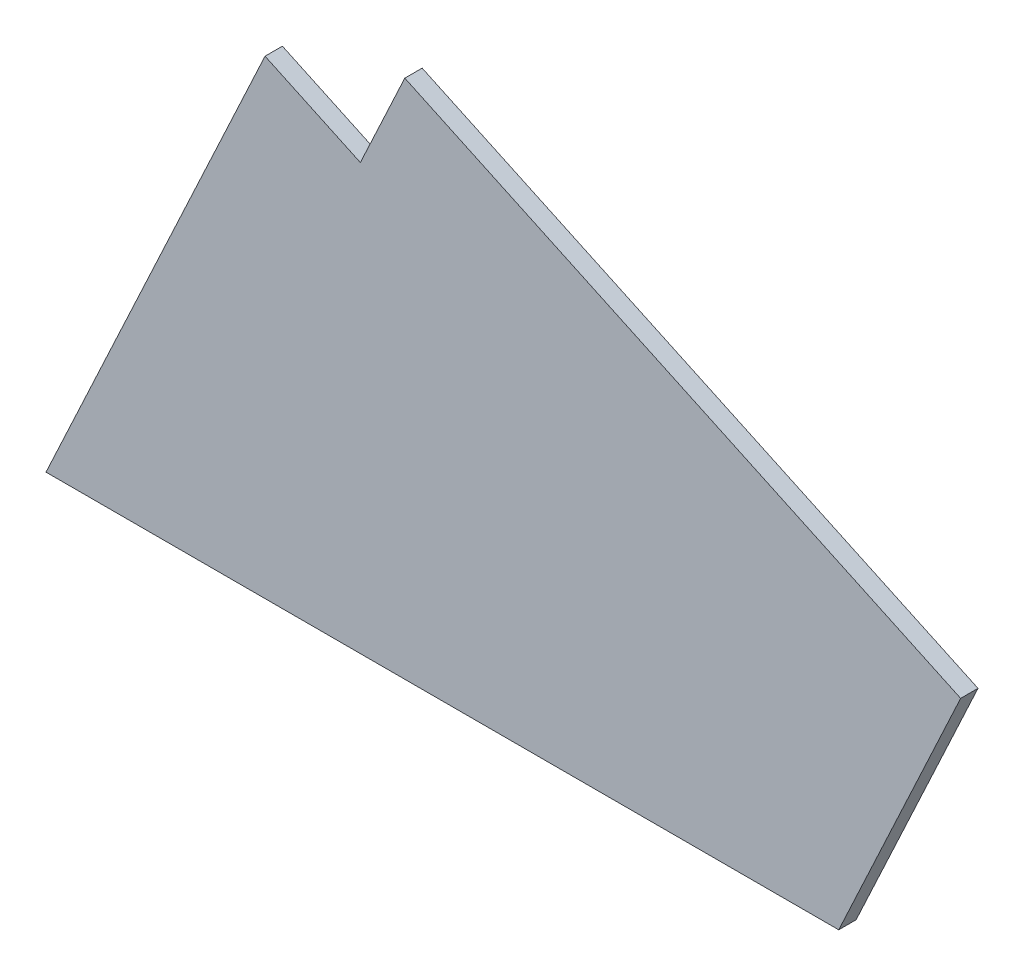
SolidWorks part; units mm, degrees
ref_plane "Front Plane" through (0, 0, 0) normal (0, 0, 1) x (1, 0, 0)
ref_plane "Top Plane" through (0, 0, 0) normal (0, 1, 0) x (1, 0, 0)
ref_plane "Right Plane" through (0, 0, 0) normal (1, 0, 0) x (0, 0, -1)
sketch "Sketch1" plane through (0, 0, 396.7) normal (0, 0, 1) x (1, 0, 0)
  line L0 (-327.4378, 0) -> (-176.6689, 0)
  line L2 (-327.4378, 0) -> (-285.7774, 89.341)
  line L3 (-285.7774, 89.341) -> (-267.6513, 80.8887)
  line L4 (-267.6513, 80.8887) -> (-259.1989, 99.0148)
  line L5 (-259.1989, 99.0148) -> (-153.4844, 49.7193)
  line L6 (-153.4844, 49.7193) -> (-176.6689, 0)
  line L7 (-176.6689, 0) -> (-153.4844, 49.7193) construction
  line L8 (-255.5737, 97.3243) -> (63.4467, -51.4373) construction
  line L9 (-327.4378, 0) -> (-176.6689, 0) construction
  line L10 (-327.4362, 0.0035) -> (-285.7774, 89.341) construction
  line L11 (-285.7774, 89.341) -> (-267.6513, 80.8887) construction
  line L12 (-267.6513, 80.8887) -> (-259.1989, 99.0148) construction
extrude "Boss-Extrude1" add sketch "Sketch1" against normal blind 3.3
